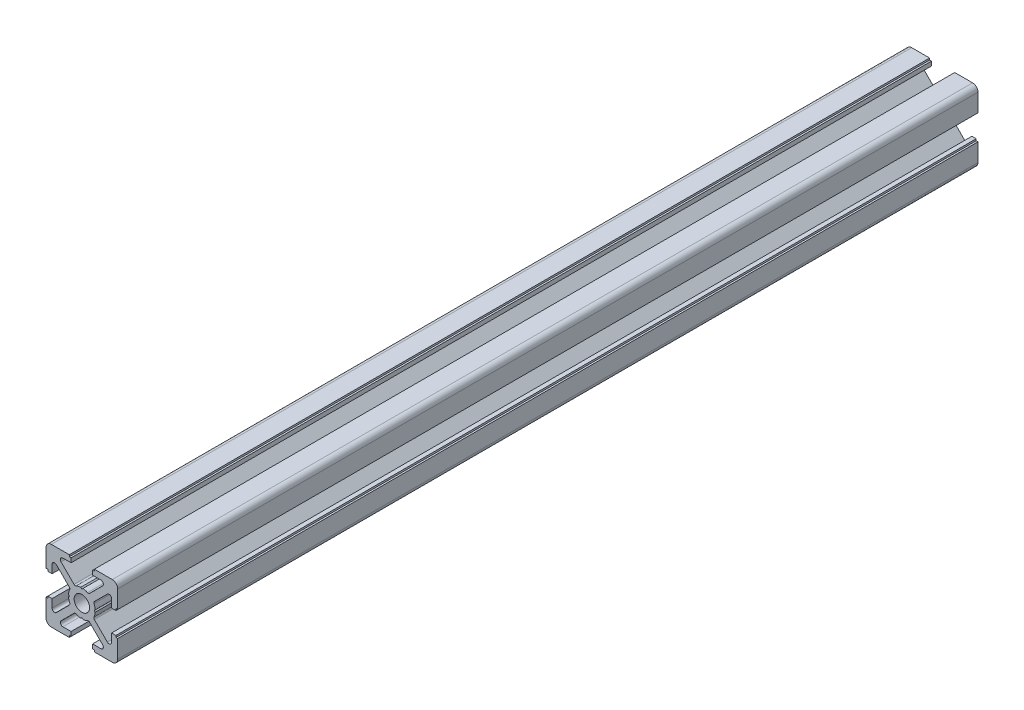
SolidWorks part; units mm, degrees
material "1060 Alloy"
ref_plane "Front Plane" through (0, 0, 0) normal (0, 0, 1) x (1, 0, 0)
ref_plane "Top Plane" through (0, 0, 0) normal (0, 1, 0) x (1, 0, 0)
ref_plane "Right Plane" through (0, 0, 0) normal (1, 0, 0) x (0, 0, -1)
ref_plane "Plane1" through (0, 0, 308) normal (0, 0, 1) x (1, 0, 0)
sketch "Sketch1" plane through (0, 0, 308) normal (0, 0, 1) x (1, 0, 0)
  line L0 (-3.5, -10) -> (-3.5, -9.5)
  line L1 (-3.5, -9.5) -> (-3, -9.5)
  line L2 (-3, -9.5) -> (-3, -8.3)
  line L3 (-3, -8.3) -> (-5.2994, -8.3)
  line L4 (-5.7944, -7.105) -> (-2.1755, -3.4861)
  line L5 (-0.3, -3.738) -> (0, -3.45)
  line L6 (0, -3.45) -> (0.3, -3.738)
  line L7 (2.1755, -3.4861) -> (5.7944, -7.105)
  line L8 (5.2994, -8.3) -> (3, -8.3)
  line L9 (3, -8.3) -> (3, -9.5)
  line L10 (3, -9.5) -> (3.5, -9.5)
  line L11 (3.5, -9.5) -> (3.5, -10)
  line L12 (3.5, -10) -> (8.5, -10)
  line L13 (10, -8.5) -> (10, -3.5)
  line L14 (10, -3.5) -> (9.5, -3.5)
  line L15 (9.5, -3.5) -> (9.5, -3)
  line L16 (9.5, -3) -> (8.3, -3)
  line L17 (8.3, -3) -> (8.3, -5.2994)
  line L18 (7.105, -5.7944) -> (3.4861, -2.1755)
  line L19 (3.738, -0.3) -> (3.45, 0)
  line L20 (3.45, 0) -> (3.738, 0.3)
  line L21 (3.4861, 2.1755) -> (7.105, 5.7944)
  line L22 (8.3, 5.2994) -> (8.3, 3)
  line L23 (8.3, 3) -> (9.5, 3)
  line L24 (9.5, 3) -> (9.5, 3.5)
  line L25 (9.5, 3.5) -> (10, 3.5)
  line L26 (10, 3.5) -> (10, 8.5)
  line L27 (8.5, 10) -> (3.5, 10)
  line L28 (3.5, 10) -> (3.5, 9.5)
  line L29 (3.5, 9.5) -> (3, 9.5)
  line L30 (3, 9.5) -> (3, 8.3)
  line L31 (3, 8.3) -> (5.2994, 8.3)
  line L32 (5.7944, 7.105) -> (2.1755, 3.4861)
  line L33 (0.3, 3.738) -> (0, 3.45)
  line L34 (0, 3.45) -> (-0.3, 3.738)
  line L35 (-2.1755, 3.4861) -> (-5.7944, 7.105)
  line L36 (-5.2994, 8.3) -> (-3, 8.3)
  line L37 (-3, 8.3) -> (-3, 9.5)
  line L38 (-3, 9.5) -> (-3.5, 9.5)
  line L39 (-3.5, 9.5) -> (-3.5, 10)
  line L40 (-3.5, 10) -> (-8.5, 10)
  line L41 (-10, 8.5) -> (-10, 3.5)
  line L42 (-10, 3.5) -> (-9.5, 3.5)
  line L43 (-9.5, 3.5) -> (-9.5, 3)
  line L44 (-9.5, 3) -> (-8.3, 3)
  line L45 (-8.3, 3) -> (-8.3, 5.2994)
  line L46 (-7.105, 5.7944) -> (-3.4861, 2.1755)
  line L47 (-3.738, 0.3) -> (-3.45, 0)
  line L48 (-3.45, 0) -> (-3.738, -0.3)
  line L49 (-3.4861, -2.1755) -> (-7.105, -5.7944)
  line L50 (-8.3, -5.2994) -> (-8.3, -3)
  line L51 (-8.3, -3) -> (-9.5, -3)
  line L52 (-9.5, -3) -> (-9.5, -3.5)
  line L53 (-9.5, -3.5) -> (-10, -3.5)
  line L54 (-10, -3.5) -> (-10, -8.5)
  line L55 (-8.5, -10) -> (-3.5, -10)
  circle A0 centre (0, 0) radius 2.15
  arc A1 (-5.2994, -8.3) -> (-5.7944, -7.105) centre (-5.2994, -7.6) cw
  arc A2 (-2.1755, -3.4861) -> (-1.6076, -3.388) centre (-1.8219, -3.8397) cw
  arc A3 (-1.6076, -3.388) -> (-0.3, -3.738) centre (0, 0) ccw
  arc A4 (0.3, -3.738) -> (1.6076, -3.388) centre (0, 0) ccw
  arc A5 (1.6076, -3.388) -> (2.1755, -3.4861) centre (1.8219, -3.8397) cw
  arc A6 (5.7944, -7.105) -> (5.2994, -8.3) centre (5.2994, -7.6) cw
  arc A7 (8.5, -10) -> (10, -8.5) centre (8.5, -8.5) ccw
  arc A8 (8.3, -5.2994) -> (7.105, -5.7944) centre (7.6, -5.2994) cw
  arc A9 (3.4861, -2.1755) -> (3.388, -1.6076) centre (3.8397, -1.8219) cw
  arc A10 (3.388, -1.6076) -> (3.738, -0.3) centre (0, 0) ccw
  arc A11 (3.738, 0.3) -> (3.388, 1.6076) centre (0, 0) ccw
  arc A12 (3.388, 1.6076) -> (3.4861, 2.1755) centre (3.8397, 1.8219) cw
  arc A13 (7.105, 5.7944) -> (8.3, 5.2994) centre (7.6, 5.2994) cw
  arc A14 (10, 8.5) -> (8.5, 10) centre (8.5, 8.5) ccw
  arc A15 (5.2994, 8.3) -> (5.7944, 7.105) centre (5.2994, 7.6) cw
  arc A16 (2.1755, 3.4861) -> (1.6076, 3.388) centre (1.8219, 3.8397) cw
  arc A17 (1.6076, 3.388) -> (0.3, 3.738) centre (0, 0) ccw
  arc A18 (-0.3, 3.738) -> (-1.6076, 3.388) centre (0, 0) ccw
  arc A19 (-1.6076, 3.388) -> (-2.1755, 3.4861) centre (-1.8219, 3.8397) cw
  arc A20 (-5.7944, 7.105) -> (-5.2994, 8.3) centre (-5.2994, 7.6) cw
  arc A21 (-8.5, 10) -> (-10, 8.5) centre (-8.5, 8.5) ccw
  arc A22 (-8.3, 5.2994) -> (-7.105, 5.7944) centre (-7.6, 5.2994) cw
  arc A23 (-3.4861, 2.1755) -> (-3.388, 1.6076) centre (-3.8397, 1.8219) cw
  arc A24 (-3.388, 1.6076) -> (-3.738, 0.3) centre (0, 0) ccw
  arc A25 (-3.738, -0.3) -> (-3.388, -1.6076) centre (0, 0) ccw
  arc A26 (-3.388, -1.6076) -> (-3.4861, -2.1755) centre (-3.8397, -1.8219) cw
  arc A27 (-7.105, -5.7944) -> (-8.3, -5.2994) centre (-7.6, -5.2994) cw
  arc A28 (-10, -8.5) -> (-8.5, -10) centre (-8.5, -8.5) ccw
extrude "Boss-Extrude1" add sketch "Sketch1" against normal blind 240
sketch "Sketch2" plane through (0, 0, 68) normal (0, 0, -1) x (-1, 0, 0)
  line L0 (-9.5, -3.5) -> (-9.5, -3) construction
  line L1 (-3.4861, 2.1755) -> (-7.105, 5.7944) construction
  line L2 (-8.3, 5.2994) -> (-8.3, 3) construction
  line L3 (-8.3, -3) -> (-8.3, -5.2994) construction
  line L4 (-7.105, -5.7944) -> (-3.4861, -2.1755) construction
  line L5 (-8.3, 3) -> (-9.5, 3) construction
  line L6 (-9.5, -3) -> (-8.3, -3) construction
  line L7 (-3.45, 0) -> (-3.738, 0.3) construction
  line L8 (-3.738, -0.3) -> (-3.45, 0) construction
  line L9 (-10, -3.5) -> (-9.5, -3.5) construction
  line L10 (-9.5, 3) -> (-9.5, 3.5) construction
  line L11 (-9.5, 3.5) -> (-10, 3.5) construction
  line L12 (-9.5, 3) -> (-9.5, 3.5)
  line L13 (-9.5, 3.5) -> (-10, 3.5)
  line L14 (-9.5, -3.5) -> (-9.5, -3)
  line L15 (-10, -3.5) -> (-9.5, -3.5)
  line L16 (-3.738, -0.3) -> (-3.45, 0)
  line L17 (-3.45, 0) -> (-3.738, 0.3)
  line L18 (-9.5, -3) -> (-8.3, -3)
  line L19 (-8.3, 3) -> (-9.5, 3)
  line L20 (-7.105, -5.7944) -> (-3.4861, -2.1755)
  line L21 (-8.3, -3) -> (-8.3, -5.2994)
  line L22 (-8.3, 5.2994) -> (-8.3, 3)
  line L23 (-3.4861, 2.1755) -> (-7.105, 5.7944)
  arc A0 (-7.105, 5.7944) -> (-8.3, 5.2994) centre (-7.6, 5.2994) ccw construction
  arc A1 (-8.3, -5.2994) -> (-7.105, -5.7944) centre (-7.6, -5.2994) ccw construction
  arc A2 (-3.4861, -2.1755) -> (-3.388, -1.6076) centre (-3.8397, -1.8219) ccw construction
  arc A3 (-3.738, -0.3) -> (-3.388, -1.6076) centre (0, 0) ccw construction
  arc A4 (-3.388, 1.6076) -> (-3.738, 0.3) centre (0, 0) ccw construction
  arc A5 (-3.388, 1.6076) -> (-3.4861, 2.1755) centre (-3.8397, 1.8219) ccw construction
  arc A6 (-3.388, 1.6076) -> (-3.4861, 2.1755) centre (-3.8397, 1.8219) ccw
  arc A7 (-3.388, 1.6076) -> (-3.738, 0.3) centre (0, 0) ccw
  arc A8 (-3.738, -0.3) -> (-3.388, -1.6076) centre (0, 0) ccw
  arc A9 (-3.4861, -2.1755) -> (-3.388, -1.6076) centre (-3.8397, -1.8219) ccw
  arc A10 (-8.3, -5.2994) -> (-7.105, -5.7944) centre (-7.6, -5.2994) ccw
  arc A11 (-7.105, 5.7944) -> (-8.3, 5.2994) centre (-7.6, 5.2994) ccw
